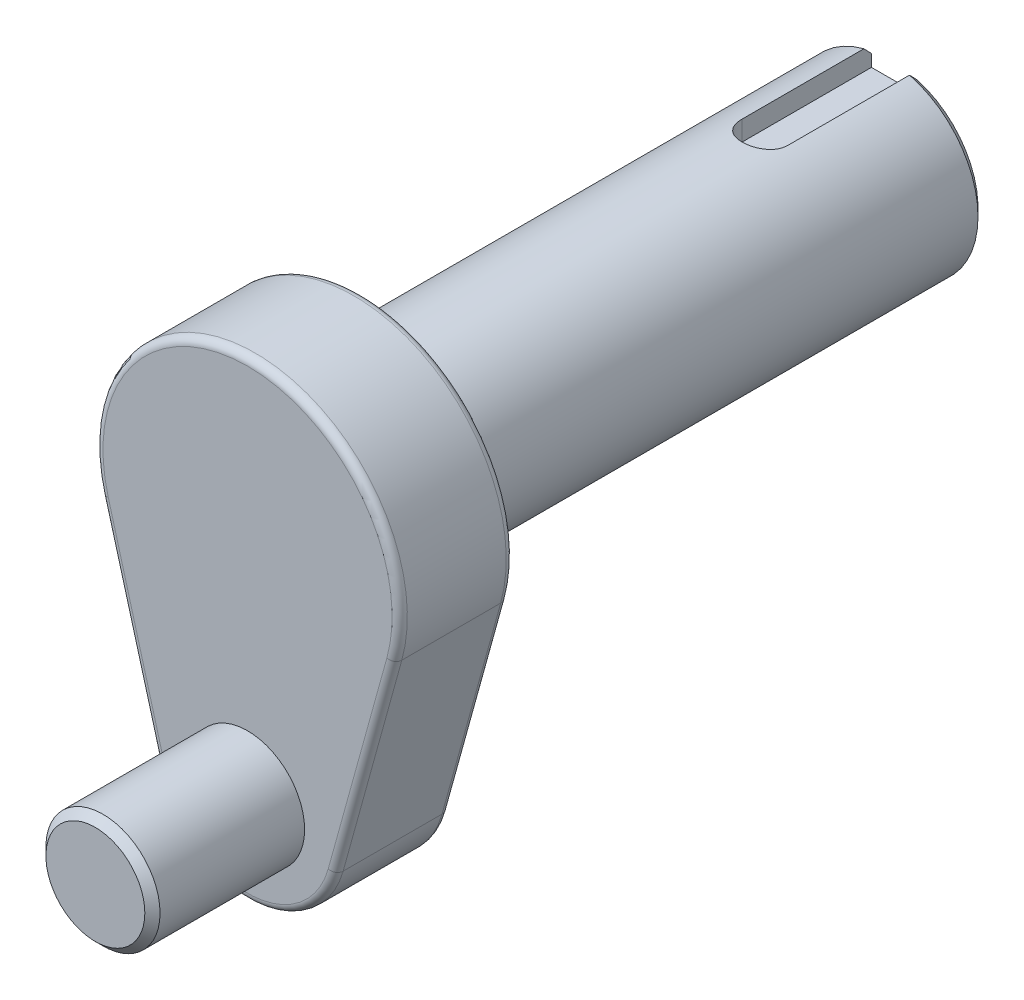
SolidWorks part; units mm, degrees
ref_plane "Front Plane" through (0, 0, 0) normal (0, 0, 1) x (1, 0, 0)
ref_plane "Top Plane" through (0, 0, 0) normal (0, 1, 0) x (1, 0, 0)
ref_plane "Right Plane" through (0, 0, 0) normal (1, 0, 0) x (0, 0, -1)
sketch "草图1" plane through (0, 0, 0) normal (0, 0, 1) x (1, 0, 0)
  circle A1 centre (0, 0) radius 6
  dimension "D1" = 12
extrude "凸台-拉伸1" add sketch "草图1" against normal blind 35
sketch "草图2" plane through (0, 0, 0) normal (0, 0, 1) x (1, 0, 0)
  line L0 (0, 0) -> (0, -15) construction
  line L1 (9.6379, -2.6667) -> (5.7827, -16.6)
  line L2 (-9.6379, -2.6667) -> (-5.7827, -16.6)
  arc A0 (9.6379, -2.6667) -> (-9.6379, -2.6667) centre (0, 0) ccw
  arc A1 (-5.7827, -16.6) -> (5.7827, -16.6) centre (0, -15) ccw
  dimension "D1" = 20
  dimension "D2" = 12
  dimension "D3" = 15
extrude "凸台-拉伸2" add sketch "草图2" along normal blind 7.5
sketch "草图3" plane through (0, 0, 7.5) normal (0, 0, 1) x (1, 0, 0)
  circle A0 centre (0, -15) radius 3.75
  dimension "D1" = 7.5
extrude "凸台-拉伸3" add sketch "草图3" along normal blind 10
chamfer "倒角1" distance 0.5 angle 45 1 edges at (3.75, -15, 17.5)
chamfer "倒角2" distance 0.5 angle 45 1 edges at (6, 0, -35)
sketch "草图5" plane through (0, 0, -35) normal (0, 0, -1) x (-1, 0, 0)
  line L1 (-1.5, 7.5) -> (1.5, 7.5)
  line L2 (-1.5, 7.5) -> (-1.5, 4.5)
  line L3 (-1.5, 4.5) -> (1.5, 4.5)
  line L4 (1.5, 7.5) -> (1.5, 4.5)
  line L5 (-1.5, 7.5) -> (1.5, 4.5) construction
  line L6 (-1.5, 4.5) -> (1.5, 7.5) construction
  circle A0 centre (0, 0) radius 6 construction
  circle A1 centre (0, 0) radius 6 construction
  point P0 (0, 6)
  dimension "D1" = 3
  dimension "D2" = 4.5
extrude "切除-拉伸1" cut sketch "草图5" against normal blind 10
fillet "圆角1" 2 edges at (-1.5, 5.1547, -25) (1.5, 5.1547, -25) type full round first side face at (-1.5, 5.1303, -30.95) second side face at (1.5, 5.2339, -30.85) middle face at (0, 5.2024, -25)
fillet "圆角2" radius 0.5 8 edges at (7.7103, -9.6333, 7.5) (0, -21, 7.5) (-7.7103, -9.6333, 7.5) (7.7103, -9.6333, 0) (0, -21, 0) (-7.7103, -9.6333, 0) (0, 10, 7.5) (0, 10, 0)
